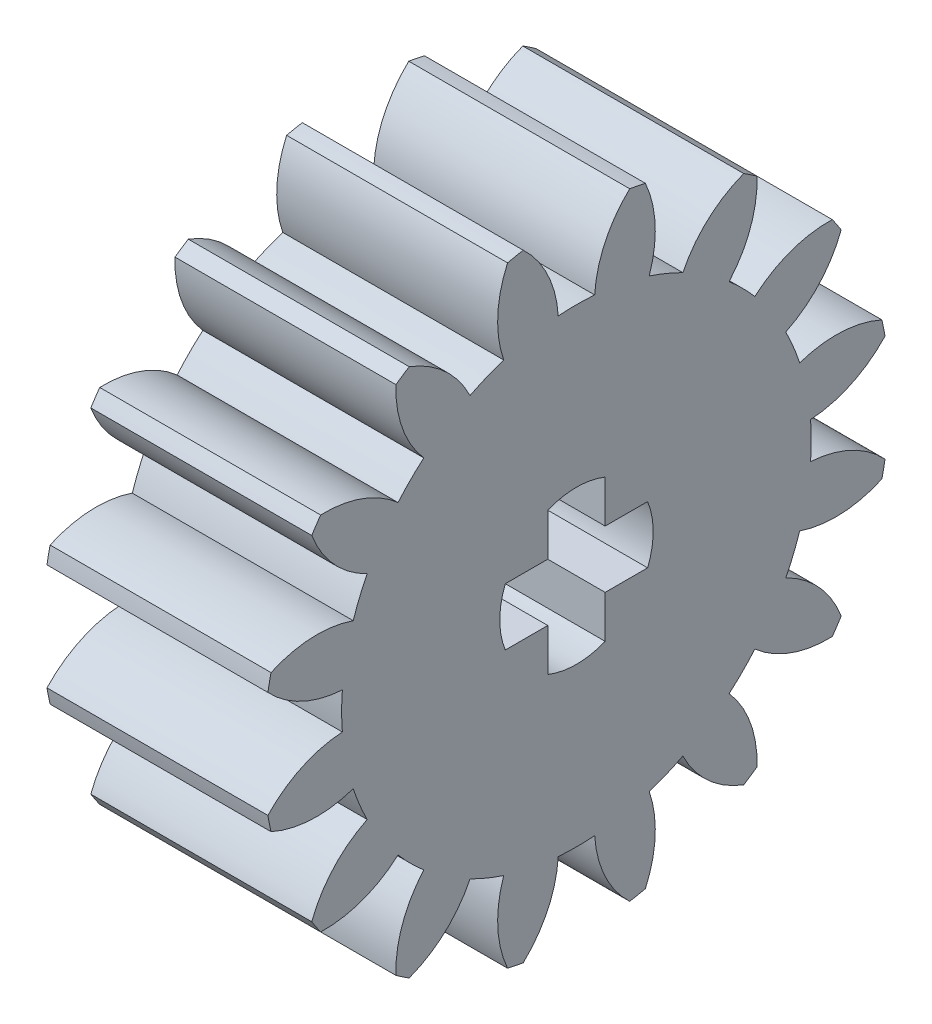
SolidWorks part; units mm, degrees
ref_plane "Plane1" through (0, 0, 0) normal (0, 0, 1) x (1, 0, 0)
ref_plane "Plane2" through (0, 0, 0) normal (0, 1, 0) x (1, 0, 0)
ref_plane "Plane3" through (0, 0, 0) normal (1, 0, 0) x (0, 0, -1)
sketch "HoldingSke" plane through (0, 0, 0) normal (0, 1, 0) x (1, 0, 0)
  line L0 (0, 0) -> (0.9613, -0.2756)
  line L1 (-15, 0) -> (100, 0) construction
  line L2 (0, 0) -> (-2.1039, 2.3779)
  line L3 (0, 0) -> (-11.863, 4.5341)
  line L4 (0, 0) -> (8.3015, 2.3804)
  line L5 (0, 0) -> (-46.8476, -17.4728)
  line L6 (0, 0) -> (-5.2639, -3.5516)
  line L7 (-2.1039, 2.3779) -> (8.6586, 51.2059)
  line L8 (-76.2, 54.61) -> (-76.1, 54.61)
  line L9 (-71.009, 38.7566) -> (-53.1078, 45.2721)
  line L10 (-76.2, 71.12) -> (104.1128, 71.12)
  line L11 (0, 0) -> (-6.35, 0)
  line L12 (-76.2, 101.6) -> (-76.162, 101.6)
  line L13 (24.9733, 27.94) -> (52.9518, 28.4284)
  line L14 (24.9733, 27.94) -> (24.9743, 27.94)
  line L15 (24.9733, 27.94) -> (100.4006, 29.5858)
  line L16 (-63.627, -1) -> (-12.827, -1)
  circle A0 centre (0, 0) radius 0.5
  circle A1 centre (0, 0) radius 6.749
  circle A2 centre (0, 0) radius 37.5
  circle A3 centre (0, 0) radius 0.5
  dimension "MHD" = 13.498
  dimension "Hub_dia" = 75
  dimension "Bore" = 1
  dimension "MBD" = 1
  dimension "Num_teeth" = 16
  dimension "Pitch_radius" = 180.3128
  dimension "Pitch" = 1
  dimension "Width" = 6.35
  dimension "Overall_len" = 50
  dimension "Show_teeth" = 16
  dimension "Thickness" = 6.35
  dimension "OAL" = 50.0001
  dimension "T_dim" = 0.1
  dimension "Ap" = 20
  dimension "H" = 19.05
  dimension "Backlash" = 0.038
  dimension "Addendum_fac" = 1
  dimension "Dedendum_fac" = 1.25
  dimension "Clearance_fac" = 0.25
  dimension "Dedendum_add" = 0.001
  dimension "Module" = 1
sketch "BasProSke" plane through (0, 0, 0) normal (0, 1, 0) x (1, 0, 0)
  line L0 (-10, 0) -> (60, 0) construction
  line L1 (0, 0) -> (0, 9)
  line L2 (0, 0) -> (6.35, 0)
  line L3 (6.35, 0) -> (6.35, 9)
  line L4 (6.35, 9) -> (0, 9)
  dimension "Diameter" = 18
  dimension "Thickness" = 6.35
revolve "Base-Revolve" add sketch "BasProSke" angle 360 about L0
sketch "TooCutSke" plane through (0, 0, 0) normal (1, 0, 0) x (0, 0, -1)
  line L1 (0, 0) -> (0, 107) construction
  line L2 (0, 0) -> (-0.8506, 7.9547) construction
  line L3 (0, 0) -> (-3.1089, 15.6293) construction
  line L4 (-0.8506, 7.9547) -> (-1.5544, 7.8146) construction
  arc A0 (0.5238, 6.7286) -> (-0.5238, 6.7286) centre (0, 0) ccw
  arc A1 (1.5534, 8.8907) -> (-1.5534, 8.8907) centre (0, 0) ccw
  circle A2 centre (0, 0) radius 8 construction
  circle A3 centre (0, 0) radius 7.5175 construction
  arc A4 (-0.5238, 6.7286) -> (-1.5534, 8.8907) centre (-3.7179, 6.5338) ccw
  arc A5 (1.5534, 8.8907) -> (0.5238, 6.7286) centre (3.7179, 6.5338) ccw
  dimension "Root_dia" = 13.498
  dimension "Overcut_dia" = 18.0508
  dimension "Pitch_dia" = 16
  dimension "Base_dia" = 15.0351
  dimension "Flank_rad" = 3.2
  dimension "Half_ang" = 11.25
  dimension "Half_CT" = 0.7176
extrude "ToothCut" cut sketch "TooCutSke" along normal through all
fillet "Breaks" [suppressed] radius 0.02 tangent propagation no
fillet "RootFillets" [suppressed] radius 0.251
pattern_circular "TeethCuts" count 16 every 22.5 about axis through (-10, 0, 0) along (1, 0, 0) of "ToothCut", "RootFillets", "Breaks"
sketch "HubNeaOneSke" plane through (0, 0, 0) normal (-1, 0, 0) x (0, 0, 1)
  circle A0 centre (0, 0) radius 6.749
  dimension "Diameter" = 13.498
extrude "HubNearOne" [suppressed] add sketch "HubNeaOneSke" along normal blind 43.6501
sketch "HubNeaBotSke" plane through (0, 0, 0) normal (-1, 0, 0) x (0, 0, 1)
  circle A0 centre (0, 0) radius 6.749
  dimension "Diameter" = 13.498
extrude "HubNearBoth" [suppressed] add sketch "HubNeaBotSke" along normal blind 21.825
ref_plane "FarPln" through (6.35, 0, 0) normal (1, 0, 0) x (0, 0, -1)
sketch "HubFarSke" plane through (6.35, 0, 0) normal (1, 0, 0) x (0, 0, -1)
  circle A0 centre (0, 0) radius 6.749
  dimension "Diameter" = 13.498
extrude "HubFar" [suppressed] add sketch "HubFarSke" along normal blind 21.825
sketch "BorSke" plane through (0, 0, 0) normal (1, 0, 0) x (0, 0, -1)
  circle A0 centre (0, 0) radius 0.5
  dimension "Diameter" = 1
extrude "Bore" cut sketch "BorSke" along normal mid plane 100.0001
sketch "KeySke" plane through (0, 0, 0) normal (1, 0, 0) x (0, 0, -1)
  line L0 (-0.05, 0) -> (-0.05, 0.6)
  line L1 (-0.05, 0.6) -> (0.05, 0.6)
  line L2 (0.05, 0.6) -> (0.05, 0)
  line L3 (0, 0) -> (0, 34) construction
  line L4 (-0.05, 0) -> (0.05, 0)
  dimension "Offset" = 0.6
  dimension "Width" = 0.1
extrude "Keyway" [suppressed] cut sketch "KeySke" along normal mid plane 100.0001
pattern_circular "Keyway2" [suppressed] count 2 every 90 about axis through (-10, 0, 0) along (1, 0, 0)
sketch "Sketch1" plane through (6.35, 0, 0) normal (1, 0, 0) x (0, 0, -1)
  line L0 (-0.8249, 2.0449) -> (-0.8249, 0.8249)
  line L1 (-0.8249, 0.8249) -> (-2.0449, 0.8249)
  line L2 (-2.0449, -0.8249) -> (-0.8249, -0.8249)
  line L3 (-0.8249, -0.8249) -> (-0.8249, -2.0449)
  line L4 (0.8249, -2.0449) -> (0.8249, -0.8249)
  line L5 (0.8249, -0.8249) -> (2.0449, -0.8249)
  line L6 (2.0449, 0.8249) -> (0.8249, 0.8249)
  line L7 (0.8249, 0.8249) -> (0.8249, 2.0449)
  circle A0 centre (0, 0) radius 2.205
  dimension "D1" = 4.41
  dimension "D2" = 1.22
extrude "Cut-Extrude1" cut sketch "Sketch1" against normal blind 10 contours L7 A0 L0 L1 L2 L3 L4 L5 L6 region at (6.35, 0, 0)
equation "' \"Module@HoldingSke\" = 6.35"
equation "' \"Num_teeth@HoldingSke\" = 12"
equation "' \"Ap@HoldingSke\" =  20"
equation "' \"Width@HoldingSke\" = 0.5 * 25.4"
equation "' \"Hub_dia@HoldingSke\"= 1 * 25.4"
equation "' \"Overall_len@HoldingSke\" = 1.0 * 25.4"
equation "' \"Bore@HoldingSke\" = 0.75 * 25.4"
equation "' \"T_dim@HoldingSke\" = 0.1 * 25.4"
equation "' \"Width@KeySke\" = 0.25 * 25.4"
equation "' \"Show_teeth@HoldingSke\" = 13"
equation "' \"Backlash@HoldingSke\" = 0.009 * 25.4"
equation "' \"Addendum_fac@HoldingSke\" = 1.0"
equation "' \"Dedendum_fac@HoldingSke\" = 1.25"
equation "' \"Dedendum_add@HoldingSke\" = 0.00005 * 25.4"
equation "' \"Clearance_fac@HoldingSke\" = 0.25"
equation "\"Pitch@HoldingSke\" = 1 / \"Module@HoldingSke\""
equation "\"Overcut_dia@TooCutSke\" = (\"Num_teeth@HoldingSke\" + 2 * \"Addendum_fac@HoldingSke\") / \"Pitch@HoldingSke\" + 0.002 * 25.4"
equation "\"Pitch_dia@TooCutSke\" = \"Num_teeth@HoldingSke\" / \"Pitch@HoldingSke\""
equation "\"Base_dia@TooCutSke\" = \"Num_teeth@HoldingSke\" / \"Pitch@HoldingSke\" * cos((\"Ap@HoldingSke\"  * 3.14159265 / 180))"
equation "\"Root_dia@TooCutSke\" = (\"Num_teeth@HoldingSke\" + 2) / \"Pitch@HoldingSke\" - 2 * (\"Addendum_fac@HoldingSke\" + \"Dedendum_fac@HoldingSke\") / \"Pitch@HoldingSke\" - \"Dedendum_add@HoldingSke\" * 2"
equation "\"Half_ang@TooCutSke\" = 180 / \"Num_teeth@HoldingSke\""
equation "\"Half_CT@TooCutSke\" = \"Num_teeth@HoldingSke\" / \"Pitch@HoldingSke\" * sin((3.14159265 / 2 / \"Num_teeth@HoldingSke\")) / 2 - 7 * \"Backlash@HoldingSke\" / 4"
equation "\"Flank_rad@TooCutSke\" = \"Num_teeth@HoldingSke\" / \"Pitch@HoldingSke\" / 5"
equation "\"Radius@RootFillets\" = \"Clearance_fac@HoldingSke\" / \"Pitch@HoldingSke\" + \"Dedendum_add@HoldingSke\""
equation "\"Break_rad@Breaks\" = 0.02 / \"Pitch@HoldingSke\""
equation "\"Thickness@HoldingSke\" = \"Width@HoldingSke\""
equation "\"OAL@HoldingSke\" = \"Thickness@HoldingSke\""
equation "\"MHD@HoldingSke\" = (\"Num_teeth@HoldingSke\" + 2) / \"Pitch@HoldingSke\" - 2 * (\"Addendum_fac@HoldingSke\" + \"Dedendum_fac@HoldingSke\")  / \"Pitch@HoldingSke\" - \"Dedendum_add@HoldingSke\" * 2"
equation "\"MBD@HoldingSke\" = (\"Num_teeth@HoldingSke\" + 2) / \"Pitch@HoldingSke\" - 2 * (\"Addendum_fac@HoldingSke\" + \"Dedendum_fac@HoldingSke\")  / \"Pitch@HoldingSke\" - \"Dedendum_add@HoldingSke\" * 2 - 0.002 * 25.4"
equation "\"MHD@HoldingSke\" = ((sgn( \"MHD@HoldingSke\" - \"Hub_dia@HoldingSke\" )-1)*( \"MHD@HoldingSke\" - \"Hub_dia@HoldingSke\" ))/-2+ \"Hub_dia@HoldingSke\""
equation "\"MBD@HoldingSke\" = ((sgn( \"MBD@HoldingSke\" - \"Bore@HoldingSke\" )-1)*( \"MBD@HoldingSke\" - \"Bore@HoldingSke\" ))/-2+ \"Bore@HoldingSke\""
equation "\"OAL@HoldingSke\" = ((sgn( \"OAL@HoldingSke\" - \"Overall_len@HoldingSke\" )+1)*( \"OAL@HoldingSke\" - \"Overall_len@HoldingSke\" ))/2 + \"Overall_len@HoldingSke\" + 0.000002 * 25.4"
equation "\"Num_teeth@TeethCuts\" = int( \"Show_teeth@HoldingSke\" ) + 1"
equation "\"Num_teeth@TeethCuts\" = ((sgn( \"Num_teeth@TeethCuts\" - \"Num_teeth@HoldingSke\" )-1)*( \"Num_teeth@TeethCuts\" - \"Num_teeth@HoldingSke\" ))/-2+ \"Num_teeth@HoldingSke\""
equation "\"Num_teeth@TeethCuts\" = ((sgn( \"Num_teeth@TeethCuts\" - 2.0)+1)*( \"Num_teeth@TeethCuts\" - 2.0))/2 +2.0"
equation "\"Angle@TeethCuts\" = 360.0 / \"Num_teeth@HoldingSke\""
equation "\"Diameter@BasProSke\" = (\"Num_teeth@HoldingSke\" + 2 * \"Addendum_fac@HoldingSke\") / \"Pitch@HoldingSke\""
equation "\"Thickness@BasProSke\"  = \"Thickness@HoldingSke\""
equation "' \"Fillet_rad@BasProSke\" =  \"Thickness@HoldingSke\" * 0.05"
equation "\"MHD@HoldingSke\" = ((sgn( \"MHD@HoldingSke\" - \"Root_dia@TooCutSke\" )-1)*( \"MHD@HoldingSke\" - \"Root_dia@TooCutSke\" ))/-2+ \"Root_dia@TooCutSke\""
equation "\"Diameter@HubNeaOneSke\" = \"MHD@HoldingSke\""
equation "\"Length@HubNearOne\" = \"OAL@HoldingSke\" - \"Thickness@BasProSke\""
equation "\"Diameter@HubNeaBotSke\" = \"MHD@HoldingSke\""
equation "\"Length@HubNearBoth\" = ( \"OAL@HoldingSke\" - \"Thickness@BasProSke\" ) / 2.0"
equation "\"Thickness@FarPln\" = \"Thickness@BasProSke\""
equation "\"Diameter@HubFarSke\" = \"MHD@HoldingSke\""
equation "\"Length@HubFar\" = ( \"OAL@HoldingSke\" - \"Thickness@BasProSke\" ) / 2.0"
equation "\"Diameter@BorSke\" = \"MBD@HoldingSke\""
equation "\"D1@Bore\" = \"OAL@HoldingSke\" * 2.0"
equation "\"D1@Keyway\" = \"OAL@HoldingSke\" * 2.0"
equation "\"Offset@KeySke\" = \"T_dim@HoldingSke\" + \"MBD@HoldingSke\" / 2.0"
